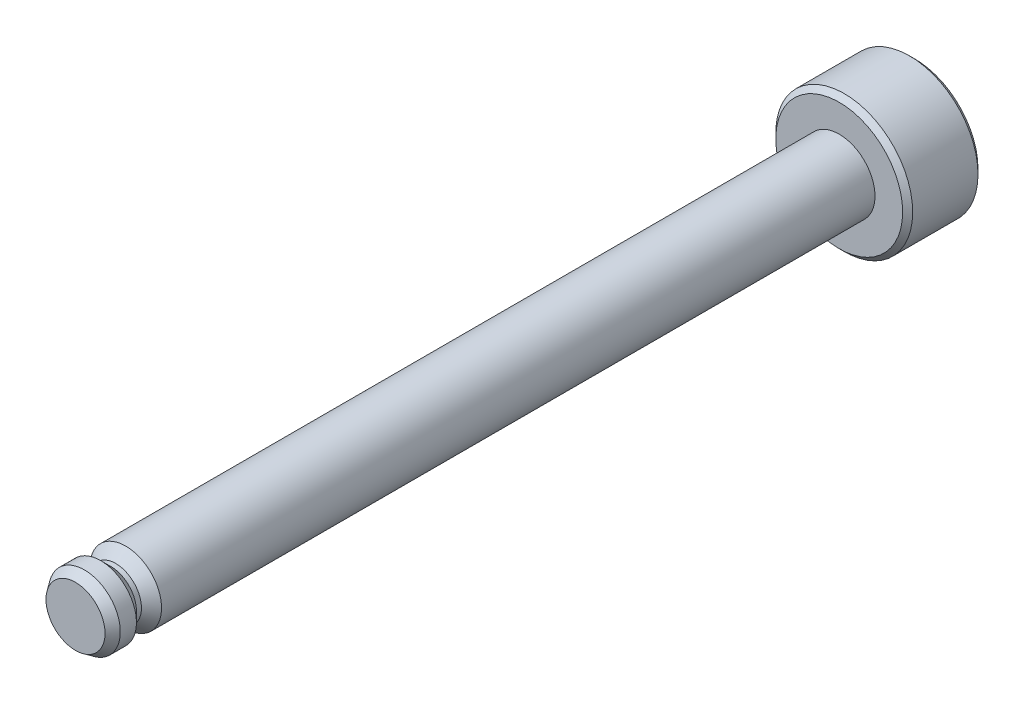
SolidWorks part; units mm, degrees
ref_plane "Front" through (0, 0, 0) normal (0, 0, 1) x (1, 0, 0)
ref_plane "Top" through (0, 0, 0) normal (0, 1, 0) x (1, 0, 0)
ref_plane "Right" through (0, 0, 0) normal (1, 0, 0) x (0, 0, -1)
sketch "Sketch2" plane through (0, 0, 0) normal (0, 0, 1) x (1, 0, 0)
  circle A0 centre (0, 0) radius 1.425
  dimension "D1" = 2.85
extrude "Shaft" add sketch "Sketch2" along normal blind 30.4
sketch "Sketch5" plane through (0, 0, 0) normal (0, 0, 1) x (1, 0, 0)
  circle A0 centre (0, 0) radius 2.725
  dimension "D1" = 5.45
extrude "Head" add sketch "Sketch5" against normal blind 3
chamfer "Chamfer1" distance 0.25 angle 55 1 edges at (1.425, 0, 30.4) first distance on face at (1.425, 0, 30.4)
chamfer "Deburs" distance 0.2 angle 45 2 edges at (2.725, 0, 0) (2.725, 0, -3)
sketch "Sketch6" plane through (0, 0, 0) normal (1, 0, 0) x (0, 0, -1)
  line L0 (0, 0) -> (-28.9, 0) construction
  line L1 (-28.9, 0) -> (-28.9, 1.025) construction
  line L2 (0, 1.425) -> (-30.043, 1.425) construction
  line L3 (-29.4, 1.425) -> (-28.4, 1.425)
  line L4 (-28.4, 1.425) -> (-28.8, 1.025)
  line L5 (-28.8, 1.025) -> (-29, 1.025)
  line L6 (-29, 1.025) -> (-29.4, 1.425)
  line L7 (-28.9, 1.025) -> (-28.9, 1.425) construction
  dimension "D1" = 28.9
  dimension "D2" = 0.4
  dimension "D3" = 1
revolve "e-Clip Notch Long" cut sketch "Sketch6" angle 360 about L0
equation "\"D1@Sketch2\"=\"Plastic Hardware OD@Box Assy.Assembly\""
equation "\"D1\"= \"Countersink Diameter@Box Assy.Assembly\" - .3mm"
equation "\"D1@Head\"=\"Countersink Depth@Box Assy.Assembly\""
equation "\"Length\"= 30mm"
equation "\"D1@Shaft\"=\"Length\"+.4mm"
equation "\"D1@Sketch6\"=\"Length\"-1.1mm"
